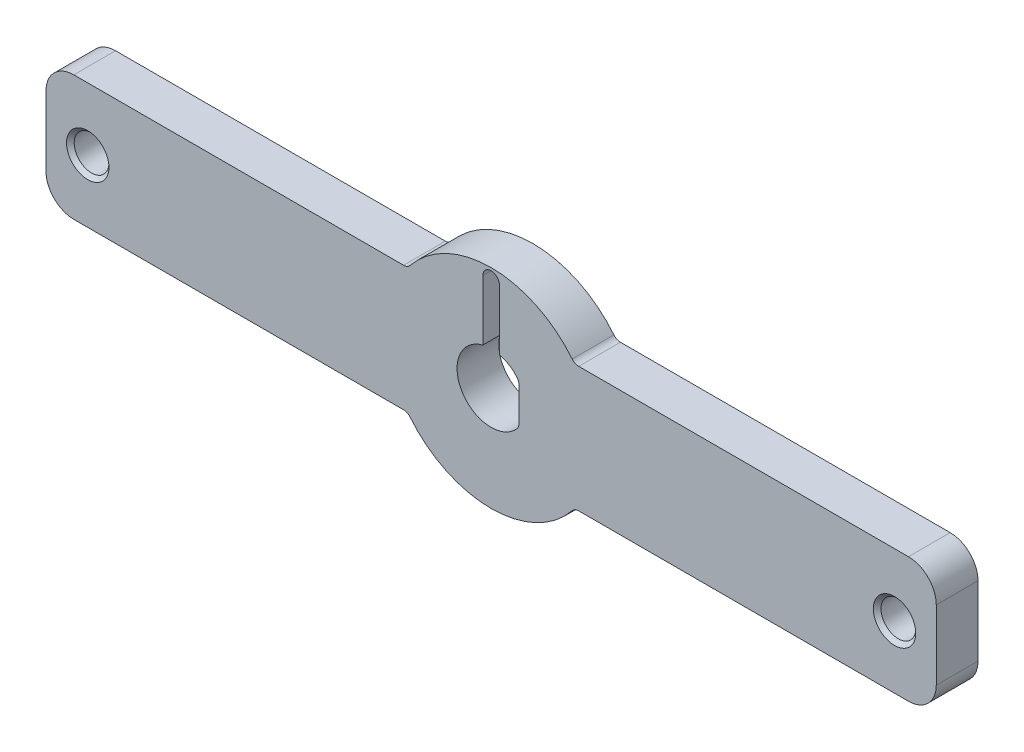
SolidWorks part; units mm, degrees
ref_plane "前视基准面" through (0, 0, 0) normal (0, 0, 1) x (1, 0, 0)
ref_plane "上视基准面" through (0, 0, 0) normal (0, 1, 0) x (1, 0, 0)
ref_plane "右视基准面" through (0, 0, 0) normal (1, 0, 0) x (0, 0, -1)
sketch "草图1" plane through (0, 0, 0) normal (0, 0, 1) x (1, 0, 0)
  line L0 (6, 4.5) -> (30, 4.5)
  line L1 (-30, 4.5) -> (-6, 4.5)
  line L2 (-32, 2.5) -> (-32, -2.5)
  line L3 (-30, -4.5) -> (-6, -4.5)
  line L4 (32, 2.5) -> (32, -2.5)
  line L5 (6, -4.5) -> (30, -4.5)
  line L6 (0.6, 7.2753) -> (0.6, 2.3754)
  line L7 (-0.6, 7.2753) -> (-0.6, 2.3754)
  line L8 (2, 1.4151) -> (2, -1.4151)
  arc A2 (30, 4.5) -> (32, 2.5) centre (30, 2.5) cw
  arc A3 (30, -4.5) -> (32, -2.5) centre (30, -2.5) ccw
  arc A4 (-32, -2.5) -> (-30, -4.5) centre (-30, -2.5) ccw
  arc A5 (-30, 4.5) -> (-32, 2.5) centre (-30, 2.5) ccw
  arc A6 (-0.6, 2.3754) -> (2, -1.4151) centre (0, 0) ccw
  arc A7 (-6, -4.5) -> (6, -4.5) centre (0, 0) ccw
  arc A8 (6, 4.5) -> (0.6818, 7.4689) centre (0, 0) ccw
  arc A9 (0.6818, 7.4689) -> (-6, 4.5) centre (0, 0) ccw
  arc A10 (2, 1.4151) -> (0.6, 2.3754) centre (0, 0) ccw
  arc A11 (0.6, 7.2753) -> (-0.6, 7.2753) centre (0, 0) ccw
  point P13 (32, 4.5)
  point P18 (-32, -4.5)
  point P21 (-32, 4.5)
  dimension "D9" = 2
  dimension "D10" = 4.9
  dimension "D11" = 15
  dimension "D15" = 14.6
  dimension "D1" = 9
  dimension "D2" = 64
  dimension "D3" = 32
  dimension "D4" = 4.5
  dimension "D12" = 0.6
  dimension "D13" = 0.6
  dimension "D14" = 2
extrude "凸台-拉伸1" add sketch "草图1" along normal blind 3
sketch "草图4" plane through (0, 0, 3) normal (0, 0, 1) x (1, 0, 0)
  point P0 (-29, 0)
  point P5 (29, 0)
hole_wizard "M3x0.5 螺纹孔1" positions "草图4" profile "草图3" tap size "M3x0.5" standard "ANSI Metric" end condition through all
sketch "草图3" plane through (-29, 0, 3) normal (1, 0, 0) x (0, -1, 0)
  line L0 (0, 0) -> (0, 3)
  line L1 (0, 3) -> (1.25, 3)
  line L2 (1.25, 3) -> (1.25, 0.275)
  line L3 (1.25, 0.275) -> (1.525, 0)
  line L5 (1.525, 0) -> (0, 0)
  line L6 (-1.25, 0.275) -> (-1.525, 0) construction
  line L11 (0, -6.35) -> (0, 107.95) construction
  dimension "通孔螺纹孔钻头直径" = 2.5
  dimension "通孔螺纹孔钻头深度" = 3
  dimension "近端锥形沉头孔直径" = 3.05
  dimension "近端锥形沉头孔角度" = 90
cosmetic thread "孔螺纹线1" parameters "D2"=3
cosmetic thread "孔螺纹线2" parameters "D2"=3
fillet "圆角1" radius 0.6 8 edges at (0.6, 7.2753, 1.5) (-0.6, 7.2753, 1.5) (2, -1.4151, 1.5) (2, 1.4151, 1.5) (-6, -4.5, 1.5) (6, -4.5, 1.5) (6, 4.5, 1.5) (-6, 4.5, 1.5)
sketch "草图5" plane through (0, 0, 0) normal (0, 0, 1) x (1, 0, 0)
  line L1 (0, 0) -> (0, 20.2748) construction
